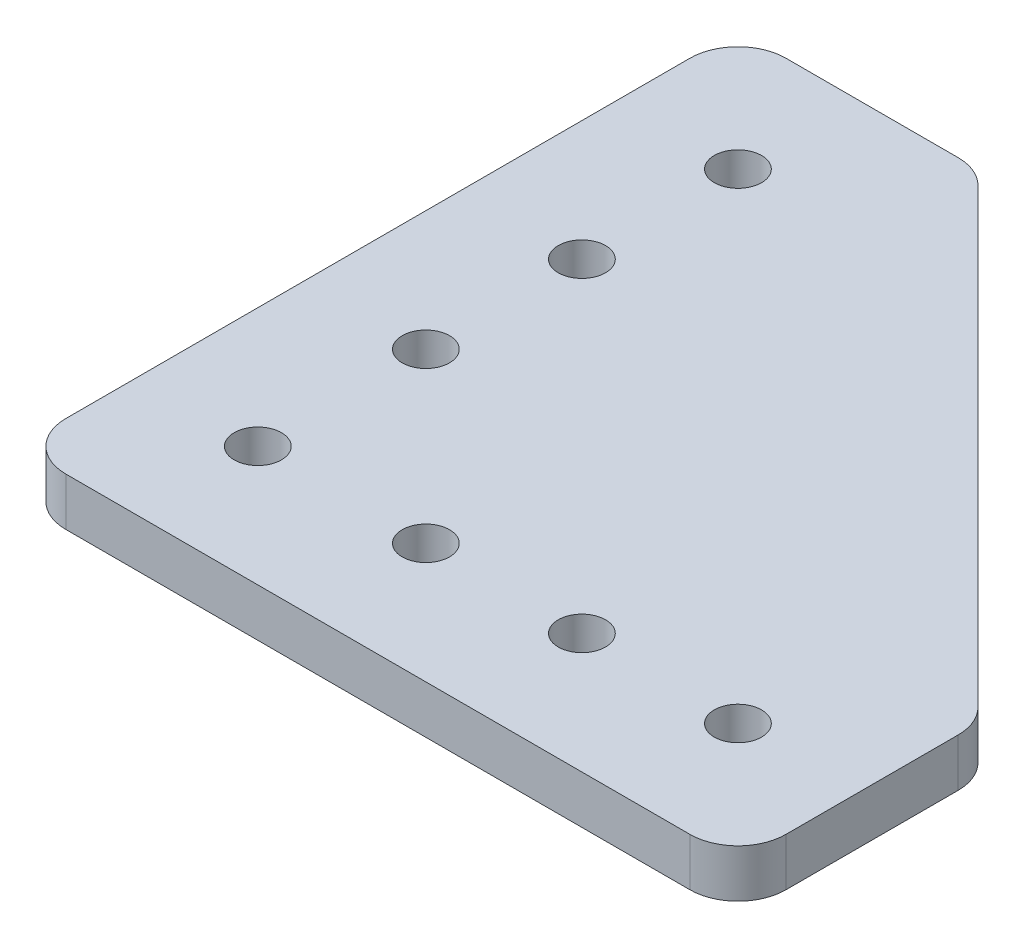
SolidWorks part; units mm, degrees
material "ABS"
ref_plane "Front Plane" through (0, 0, 0) normal (0, 0, 1) x (1, 0, 0)
ref_plane "Top Plane" through (0, 0, 0) normal (0, 1, 0) x (1, 0, 0)
ref_plane "Right Plane" through (0, 0, 0) normal (1, 0, 0) x (0, 0, -1)
sketch "Sketch1" plane through (0, 0, 0) normal (0, 1, 0) x (1, 0, 0)
  line L0 (0, 0) -> (0, 76.2)
  line L1 (0, 76.2) -> (25.4, 76.2)
  line L2 (25.4, 76.2) -> (76.2, 25.4)
  line L3 (76.2, 25.4) -> (76.2, 0)
  line L4 (76.2, 0) -> (0, 0)
  line L5 (25.4, 76.2) -> (25.4, 25.4) construction
  line L6 (25.4, 25.4) -> (76.2, 25.4) construction
  line L7 (76.2, 12.7) -> (12.7, 12.7) construction
  line L8 (12.7, 12.7) -> (12.7, 76.2) construction
  circle A0 centre (12.7, 63.5) radius 2.5
  circle A1 centre (63.5, 12.7) radius 2.5
  circle A2 centre (12.7, 46.99) radius 2.5
  circle A3 centre (12.7, 30.48) radius 2.5
  circle A4 centre (46.99, 12.7) radius 2.5
  circle A5 centre (30.48, 12.7) radius 2.5
  circle A6 centre (12.7, 12.7) radius 2.5
  dimension "D3" = 5
  dimension "D1" = 25.4
  dimension "D2" = 76.2
  dimension "D4" = 12.7
  dimension "D5" = 12.7
  dimension "D6" = 3
  dimension "D7" = 3
extrude "Boss-Extrude1" add sketch "Sketch1" along normal blind 5.08
fillet "Fillet1" radius 5.08 1 edges at (0, 2.54, 0)
fillet "Fillet2" radius 5.08 4 edges at (25.4, 2.54, -76.2) (0, 2.54, -76.2) (76.2, 2.54, 0) (76.2, 2.54, -25.4)
